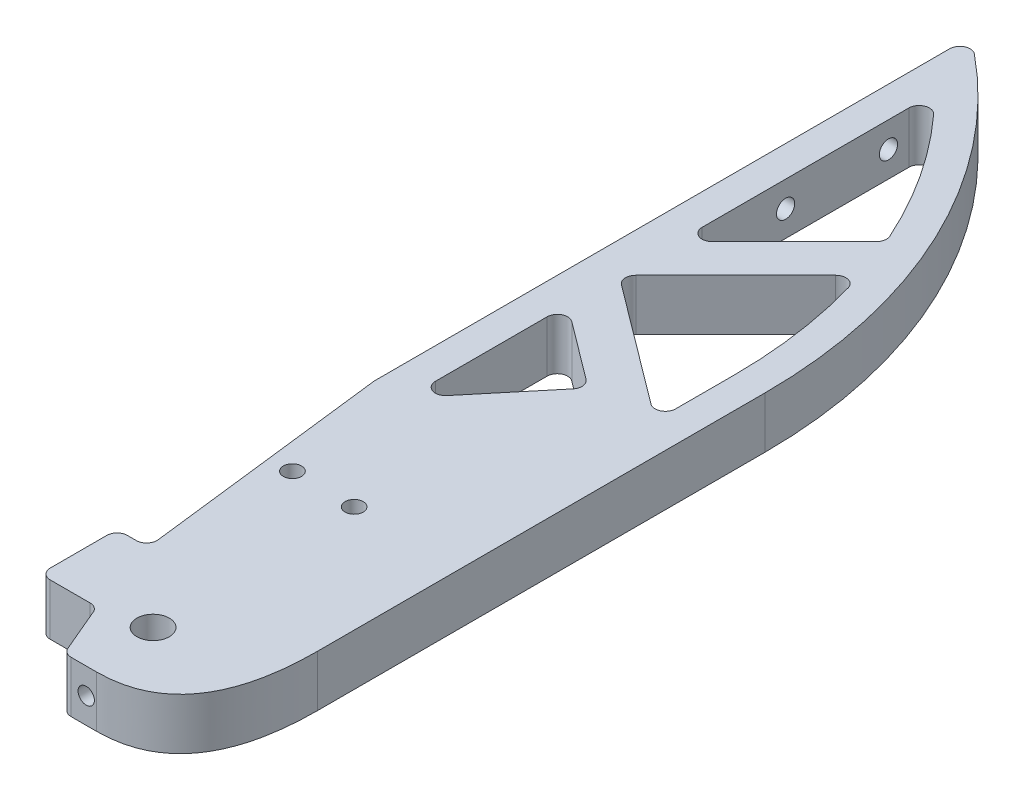
SolidWorks part; units mm, degrees
ref_plane "Front Plane" through (0, 0, 0) normal (0, 0, 1) x (1, 0, 0)
ref_plane "Top Plane" through (0, 0, 0) normal (0, 1, 0) x (1, 0, 0)
ref_plane "Right Plane" through (0, 0, 0) normal (1, 0, 0) x (0, 0, -1)
sketch "Sketch1" plane through (0, 0, 0) normal (0, 1, 0) x (1, 0, 0)
  line L1 (-25.4, -121.92) -> (25.4, -121.92)
  line L2 (-25.4, -121.92) -> (-25.4, 121.92)
  line L3 (-25.4, 121.92) -> (25.4, 121.92)
  line L4 (25.4, -121.92) -> (25.4, 121.92)
  line L5 (-25.4, -121.92) -> (25.4, 121.92) construction
  line L6 (-25.4, 121.92) -> (25.4, -121.92) construction
  point P0 (0, 0)
  dimension "D1" = 243.84
  dimension "D2" = 50.8
extrude "Boss-Extrude1" add sketch "Sketch1" along normal mid plane 12.7
sketch "Sketch2" plane through (0, 6.35, 0) normal (0, 1, 0) x (1, 0, 0)
  line L0 (0, 121.92) -> (0, -121.92) construction
  line L1 (25.4, 121.92) -> (-25.4, 121.92) construction
  line L2 (-25.4, -121.92) -> (25.4, -121.92) construction
  circle A0 centre (0, -105.41) radius 4
  dimension "D1" = 8
  dimension "D2" = 16.51
extrude "Pivot Point" cut sketch "Sketch2" against normal through all
sketch "Sketch3" plane through (0, 6.35, 0) normal (0, 1, 0) x (1, 0, 0)
  line L0 (0, -105.41) -> (0, -113.03) construction
  line L1 (0, -113.03) -> (-25.4, -113.03) construction
  line L2 (-25.4, 121.92) -> (-25.4, -121.92) construction
  line L3 (-25.4, -113.03) -> (-11.176, -113.03) construction
  line L4 (-11.176, -113.03) -> (-11.176, -121.92) construction
  line L5 (-25.4, -121.92) -> (25.4, -121.92) construction
  line L6 (-25.4, -107.95) -> (-9.8374, -107.95)
  line L7 (-9.8374, -107.95) -> (0, -105.41) construction
  line L8 (-6.7202, -113.03) -> (-2.9466, -121.92) construction
  line L10 (-25.4, -88.9) -> (-17.78, -88.9)
  line L11 (-17.78, -88.9) -> (-25.4, -25.4)
  line L12 (-25.4, -25.4) -> (-25.4, 121.92)
  line L13 (-25.4, 121.92) -> (25.4, 121.92)
  line L14 (25.4, 121.92) -> (25.4, 20.32)
  line L15 (25.4, -121.92) -> (25.4, 121.92) construction
  line L16 (25.4, -90.17) -> (25.4, -121.92)
  line L17 (25.4, -121.92) -> (2.54, -121.92)
  line L18 (-2.9466, -121.92) -> (-25.4, -121.92) construction
  line L19 (-25.4, -121.92) -> (-25.4, -25.4)
  line L21 (-11.3324, -107.95) -> (-5.4025, -121.92)
  line L22 (-5.4025, -121.92) -> (-25.4, -121.92)
  circle A0 centre (0, -105.41) radius 10.16 construction
  arc A1 (-9.8374, -107.95) -> (-6.7202, -113.03) centre (0, -105.41) ccw
  arc A2 (-25.4, 121.92) -> (25.4, 20.32) centre (-101.6, 20.32) cw
  spline S0 degree 2 poles (2.54, -121.92) (25.4, -121.92) (25.4, -90.17) knots 0 0 0 1 1 1
  line M22 (-25.4, 121.92) -> (-25.4, -121.92)
  line M23 (-25.4, -121.92) -> (25.4, -121.92)
  dimension "D1" = 7.62
  dimension "D4" = 20.32
  dimension "D6" = 7.62
  dimension "D7" = 63.5
  dimension "D9" = 31.75
  dimension "D10" = 22.86
  dimension "D11" = 101.6
  dimension "D12" = 2.2606
  dimension "D2" = 11.176
  dimension "D3" = 5.08
  dimension "D5" = 113
  dimension "D8" = 19.05
extrude "Main Shape" cut sketch "Sketch3" against normal through all contours A1 L6 L8 M22 M23 | L10 L11 M22 | S0 L16 L17 | A2 L14 L13 region at (-16.7977, 6.35, 115.3403) region at (-22.86, 6.35, 67.7333)
sketch "Sketch12" plane through (-25.4, 0, 0) normal (-1, 0, 0) x (0, 0, 1)
  line L0 (-93.98, 0) -> (-68.58, 0)
  line L1 (-121.92, 6.35) -> (-121.92, -6.35) construction
  point P0 (-93.98, 0)
  point P2 (-68.58, 0)
  point P9 (-121.92, 0)
  dimension "D1" = 25.4
  dimension "D2" = 27.94
sketch "Sketch4" plane through (0, 6.35, 0) normal (0, 1, 0) x (1, 0, 0)
  line L0 (-17.78, 105.3247) -> (-17.78, 41.8247)
  line L1 (-17.78, 41.8247) -> (8.0114, 67.6161)
  line L2 (11.9462, 57.1825) -> (-17.78, 27.4562)
  line L3 (-17.78, 27.4562) -> (17.78, 0.7862)
  line L4 (17.78, 0.7862) -> (17.78, 20.32)
  line L5 (-17.78, 14.7562) -> (2.54, -0.4838)
  line L6 (2.54, -0.4838) -> (-17.78, -24.9444)
  line L7 (-17.78, -24.9444) -> (-17.78, 14.7562)
  line L10 (-9.1909, -96.52) -> (-17.78, -96.52)
  line L11 (-9.1909, -96.52) -> (-17.78, -96.52)
  line L12 (-17.78, -96.52) -> (-17.78, -100.33)
  line L13 (-17.78, -96.52) -> (-17.78, -100.33)
  line L32 (17.78, -90.17) -> (17.78, 20.32)
  line L33 (-17.78, 105.3247) -> (-17.78, -24.9444)
  line L34 (-17.78, -24.9444) -> (-9.1909, -96.52)
  line L37 (-17.78, -100.33) -> (-6.2888, -100.33)
  line L38 (-6.2888, -100.33) -> (-0.3589, -114.3)
  line L39 (-0.3589, -114.3) -> (2.54, -114.3)
  line L40 (17.78, -90.17) -> (17.78, 20.32) construction
  line L41 (-17.78, 105.3247) -> (-17.78, -24.9444) construction
  line L42 (-17.78, -24.9444) -> (-9.1909, -96.52) construction
  line L45 (-17.78, -100.33) -> (-6.2888, -100.33) construction
  line L46 (-6.2888, -100.33) -> (-0.3589, -114.3) construction
  line L47 (-0.3589, -114.3) -> (2.54, -114.3) construction
  arc A0 (-17.78, 105.3247) -> (8.0114, 67.6161) centre (-101.6, 20.32) cw
  arc A1 (11.9462, 57.1825) -> (17.78, 20.32) centre (-101.6, 20.32) cw
  arc A4 (17.78, 20.32) -> (-17.78, 105.3247) centre (-101.6, 20.32) ccw
  arc A5 (17.78, 20.32) -> (-17.78, 105.3247) centre (-101.6, 20.32) ccw construction
  spline S0 degree 3 poles (182.3768, -3106.4872) (-121.3578, 113.6597) (-43.6576, -124.5249) (6.9357, -113.8408) (7.2696, -113.7586) (7.9257, -113.5702) (8.8946, -113.2517) (9.8134, -112.8132) (10.6914, -112.2772) (10.9756, -112.0829) (11.5168, -111.6709) (11.7754, -111.4522) (12.5172, -110.76) (12.967, -110.2498) (13.7869, -109.1494) (14.1472, -108.5738) (14.7943, -107.3847) (15.0809, -106.7713) (15.5964, -105.5147) (15.8257, -104.8691) (16.2318, -103.5721) (16.4093, -102.9189) (16.8809, -100.9486) (17.1147, -99.6205) (17.47, -96.9442) (17.5908, -95.5951) (23.2835, 3.8327) (-199.485, 108.5636) (3001.6783, 113.4716) knots -4.573947 -4.573947 -4.573947 -4.573947 0.125 0.125 0.15625 0.15625 0.1875 0.25 0.25 0.28125 0.28125 0.3125 0.3125 0.375 0.375 0.4375 0.4375 0.5 0.5 0.5625 0.5625 0.625 0.625 0.75 0.75 0.875 0.875 9.919668 9.919668 9.919668 9.919668 only from (2.54, -114.3) to (17.78, -90.17)
  spline S1 degree 3 poles (2.54, -114.3) (3.9081, -114.3) (5.2645, -114.1937) (6.9357, -113.8408) (7.2696, -113.7586) (7.9257, -113.5702) (8.8946, -113.2517) (9.8134, -112.8132) (10.6914, -112.2772) (10.9756, -112.0829) (11.5168, -111.6709) (11.7754, -111.4522) (12.5172, -110.76) (12.967, -110.2498) (13.7869, -109.1494) (14.1472, -108.5738) (14.7943, -107.3847) (15.0809, -106.7713) (15.5964, -105.5147) (15.8257, -104.8691) (16.2318, -103.5721) (16.4093, -102.9189) (16.8809, -100.9486) (17.1147, -99.6205) (17.47, -96.9442) (17.5908, -95.5951) (17.746, -92.8843) (17.78, -91.5277) (17.78, -90.17) knots 0 0 0 0 0.125 0.125 0.15625 0.15625 0.1875 0.25 0.25 0.28125 0.28125 0.3125 0.3125 0.375 0.375 0.4375 0.4375 0.5 0.5 0.5625 0.5625 0.625 0.625 0.75 0.75 0.875 0.875 1 1 1 1 construction
  dimension "D2" = 119.38
  dimension "D3" = 45
  dimension "D4" = 63.5
  dimension "D5" = 10.16
  dimension "D6" = 44.45
  dimension "D7" = 25.4
  dimension "D8" = 10.16
  dimension "D1" = 7.62
extrude "Optimizing Weight Cutout" cut sketch "Sketch4" against normal through all contours A1 L2 L3 L4 | L7 L6 L5 | L1 A0 L0 region at (5.0566, 6.35, -28.7141) region at (-11.0067, 6.35, 3.5573)
hole_wizard "#8 Clearance Hole1" positions "Sketch12" profile "Sketch11" hole size "#8" standard "ANSI Inch" end condition up to next
sketch "Sketch11" plane through (-25.4, 0, -93.98) normal (0, 1, 0) x (0, 0, 1)
  line L0 (0, 0) -> (0, 27.2563)
  line L1 (0, 27.2563) -> (2.2479, 27.2563)
  line L2 (2.2479, 27.2563) -> (2.2479, 0)
  line L5 (2.2479, 0) -> (0, 0)
  line L11 (0, -6.35) -> (0, 107.95) construction
  dimension "Thru Hole Dia." = 4.4958
  dimension "Thru Hole Depth" = 27.2563
sketch "Sketch7" plane through (0, 0, 121.92) normal (0, 0, 1) x (1, 0, 0)
  point P0 (0, 0)
hole_wizard "#10-32 Tapped Hole1" positions "Sketch7" profile "Sketch8" tap size "#10-32" standard "ANSI Inch"
sketch "Sketch8" plane through (0, 0, 121.92) normal (1, 0, 0) x (0, -1, 0)
  line L0 (0, 0) -> (0, 15.1833)
  line L1 (0, 15.1833) -> (2.0193, 13.97)
  line L2 (2.0193, 13.97) -> (2.0193, 0)
  line L5 (2.0193, 0) -> (0, 0)
  line L10 (0, 15.1833) -> (-2.0193, 13.97) construction
  line L11 (0, -6.35) -> (0, 107.95) construction
  dimension "Tap Drill Dia." = 4.0386
  dimension "Tap Drill Depth" = 13.97
  dimension "Drill Angle" = 118
cosmetic thread "Hole Thread1" parameters "D1"=9.652, "D2"=4.826
sketch "Set Screw Ref" plane through (0, 6.35, 0) normal (0, 1, 0) x (1, 0, 0)
  line L0 (0, -105.41) -> (0, -121.92) construction
  line L1 (-5.4025, -121.92) -> (2.54, -121.92) construction
  line L2 (0, -121.92) -> (0, -107.505)
  line L3 (0, -109.41) -> (1.778, -109.41)
  circle A0 centre (0, -105.41) radius 4 construction
  dimension "D1" = 1.905
  dimension "D2" = 1.778
fillet "Fillet1" radius 2.54 15 edges at (-17.78, 0, 88.9) (-25.4, 0, 88.9) (-25.4, 0, 107.95) (-5.4025, 0, 121.92) (-25.4, 0, -121.92) (-17.78, 0, -105.3247) (-17.78, 0, -41.8247) (8.0114, 0, -67.6161) (11.9462, 0, -57.1825) (-17.78, 0, -14.7562) (2.54, 0, 0.4838) (-17.78, 0, 24.9444) (17.78, 0, -0.7862) (-17.78, 0, -27.4562) (-11.3324, 0, 107.95)
sketch "Sketch15" plane through (0, 6.35, 0) normal (0, 1, 0) x (1, 0, 0)
  line L0 (-16.2052, -54.7915) -> (-0.9652, -54.7915)
  line L3 (25.4, -90.17) -> (25.4, 20.32) construction
  point P67 (-16.2052, -54.7915)
  point P70 (-0.9652, -54.7915)
  point P76 (-0.9713, -54.7914)
  point P79 (-0.9713, -54.7914)
  point P80 (-16.2113, -54.7914)
  point P81 (-0.9713, -54.7914)
  point P86 (0, 0)
  dimension "D1" = 15.24
  dimension "D2" = 54.8
  dimension "D3" = 26.3652
hole_wizard "#8 Clearance Hole2" positions "Sketch15" profile "Sketch14" hole size "#8" standard "ANSI Inch" end condition through all
sketch "Sketch14" plane through (-16.2052, 6.35, 54.7915) normal (1, 0, 0) x (0, 0, 1)
  line L0 (0, 0) -> (0, 12.7)
  line L1 (0, 12.7) -> (2.2479, 12.7)
  line L2 (2.2479, 12.7) -> (2.2479, 0)
  line L5 (2.2479, 0) -> (0, 0)
  line L11 (0, -6.35) -> (0, 107.95) construction
  dimension "Thru Hole Dia." = 4.4958
  dimension "Thru Hole Depth" = 12.7
